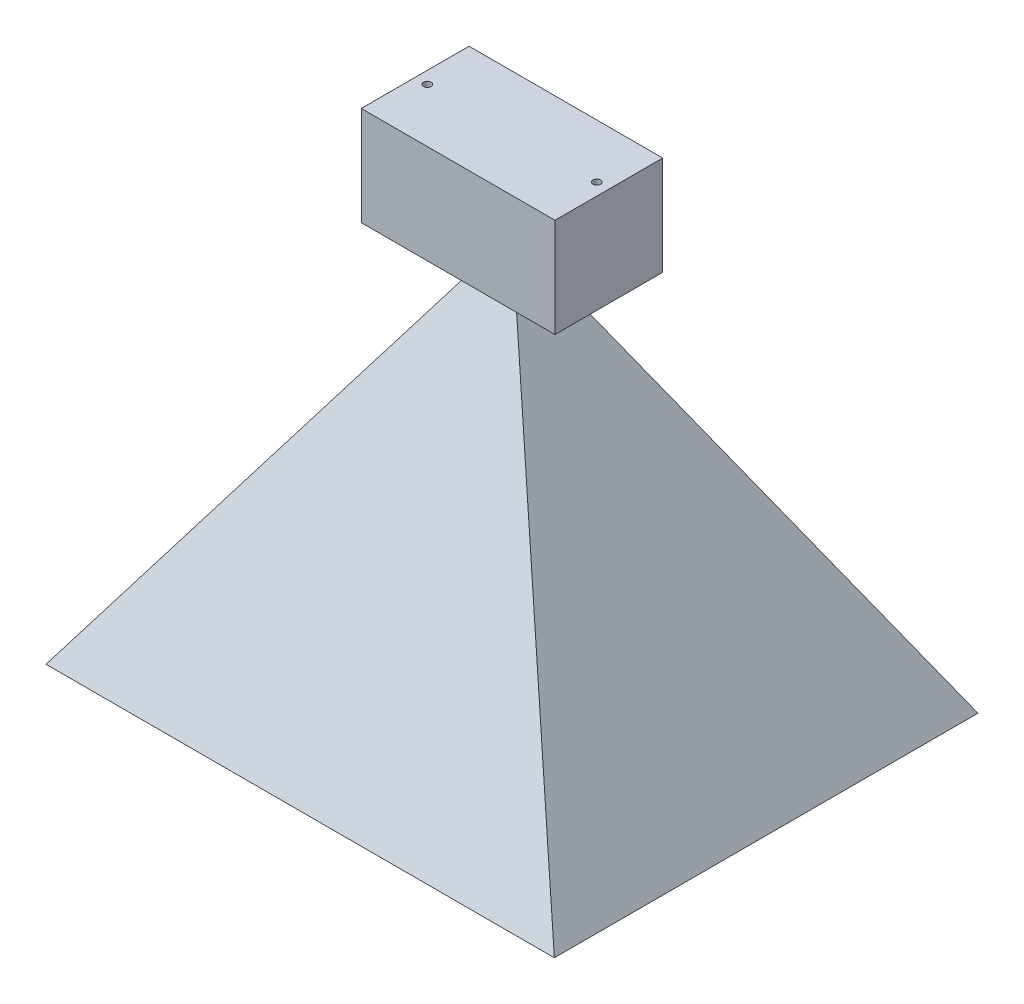
SolidWorks part; units mm, degrees
ref_plane "Front Plane" through (0, 0, 0) normal (0, 0, 1) x (1, 0, 0)
ref_plane "Top Plane" through (0, 0, 0) normal (0, 1, 0) x (1, 0, 0)
ref_plane "Right Plane" through (0, 0, 0) normal (1, 0, 0) x (0, 0, -1)
ref_plane "distance of measurement" through (0, 114.3, 0) normal (0, 1, 0) x (1, 0, 0)
sketch "Sketch1" plane through (0, 0, 0) normal (0, 1, 0) x (1, 0, 0)
  line L1 (-76.2, -63.5) -> (76.2, -63.5)
  line L2 (-76.2, -63.5) -> (-76.2, 63.5)
  line L3 (-76.2, 63.5) -> (76.2, 63.5)
  line L4 (76.2, -63.5) -> (76.2, 63.5)
  line L5 (-76.2, -63.5) -> (76.2, 63.5) construction
  line L6 (-76.2, 63.5) -> (76.2, -63.5) construction
  point P0 (0, 0)
  dimension "D1" = 152.4
  dimension "D2" = 127
sketch "Sketch2" plane through (0, 114.3, 0) normal (0, 1, 0) x (1, 0, 0)
  line L0 (-76.2, -63.5) -> (76.2, 63.5) construction
  line L1 (-2.4698, -2.0581) -> (2.4698, -2.0581)
  line L2 (-2.4698, -2.0581) -> (-2.4698, 2.0581)
  line L3 (-2.4698, 2.0581) -> (2.4698, 2.0581)
  line L4 (2.4698, -2.0581) -> (2.4698, 2.0581)
  line L5 (-2.4698, -2.0581) -> (2.4698, 2.0581) construction
  line L6 (-2.4698, 2.0581) -> (2.4698, -2.0581) construction
  point P0 (0, 0)
loft "FOV" add profiles "Sketch2", "Sketch1" connector at (-2.4698, 114.3, 2.0581) connector at (-76.2, 0, 63.5)
sketch "Sketch3" plane through (0, 114.3, 0) normal (0, 1, 0) x (1, 0, 0)
  circle A0 centre (0, 0) radius 8.509
  dimension "D1" = 17.018
extrude "camera lens" add sketch "Sketch3" along normal blind 0.254
sketch "Sketch4" plane through (0, 114.554, 0) normal (0, 1, 0) x (1, 0, 0)
  line L1 (29.0322, -16.1544) -> (-29.0322, -16.1544)
  line L2 (29.0322, -16.1544) -> (29.0322, 16.1544)
  line L3 (29.0322, 16.1544) -> (-29.0322, 16.1544)
  line L4 (-29.0322, -16.1544) -> (-29.0322, 16.1544)
  line L5 (29.0322, -16.1544) -> (-29.0322, 16.1544) construction
  line L6 (29.0322, 16.1544) -> (-29.0322, -16.1544) construction
  point P0 (0, 0)
  dimension "D1" = 58.0644
  dimension "D2" = 32.3088
extrude "camera holder" add sketch "Sketch4" along normal blind 29.6672
ref_point "centre of vision"
ref_point "direction reference"
sketch "reference points sketch" plane through (0, 0, 0) normal (0, -1, 0) x (1, 0, 0)
  line L0 (-76.2, 63.5) -> (76.2, 63.5) construction
  line L1 (76.2, 63.5) -> (76.2, -63.5) construction
  line L2 (76.2, -63.5) -> (-76.2, -63.5) construction
  line L3 (-76.2, -63.5) -> (-76.2, 63.5) construction
  line L4 (-76.2, 63.5) -> (76.2, -63.5) construction
  line L5 (-76.2, -63.5) -> (76.2, 63.5) construction
  point P0 (0, 63.5)
  point P1 (76.2, 0)
  point P4 (0, -63.5)
  point P7 (-76.2, 0)
  point P10 (-38.1, 0)
  point P13 (38.1, 0)
  point P14 (0, 31.75)
  point P15 (0, -31.75)
  point P16 (38.1, -31.75)
  point P17 (38.1, 31.75)
  point P20 (-38.1, 31.75)
  point P23 (-38.1, -31.75)
  point P24 (-76.2, 63.5)
  point P26 (76.2, 63.5)
  point P28 (76.2, -63.5)
  point P30 (-76.2, -63.5)
  dimension "D1" = 31.75
  dimension "D2" = 0
  dimension "D3" = 38.1
  dimension "D4" = 31.75
  dimension "D5" = 31.75
  dimension "D6" = 38.1
  dimension "D7" = 38.1
  dimension "D8" = 31.75
  dimension "D9" = 38.1
  dimension "D10" = 31.75
  dimension "D11" = 38.1
  dimension "D12" = 38.1
ref_point "direction reference 0"
ref_point "direction reference 1"
ref_point "direction reference 2"
ref_point "direction reference 3"
ref_point "direction reference 4"
ref_point "direction reference 5"
ref_point "direction reference 6"
ref_point "direction reference 7"
ref_point "direction reference 8"
ref_point "direction reference 9"
ref_point "direction reference 10"
ref_point "direction reference 11"
ref_point "direction reference 12"
ref_point "direction reference 13"
ref_point "direction reference 14"
ref_point "direction reference 15"
hole_wizard "#4-40 Tapped Hole1" positions "Sketch6" profile "Sketch5" tap size "#4-40" standard "ANSI Inch" end condition up to next
sketch "Sketch6" plane through (0, 144.2212, 0) normal (0, 1, 0) x (1, 0, 0)
  point P0 (-25.4, 0)
  point P2 (25.4, 0)
  dimension "D1" = 25.4
  dimension "D2" = 25.4
sketch "Sketch5" plane through (-25.4, 144.2212, 0) normal (1, 0, 0) x (0, 0, 1)
  line L0 (0, 0) -> (0, 29.6672)
  line L1 (0, 29.6672) -> (1.1303, 29.6672)
  line L2 (1.1303, 29.6672) -> (1.1303, 0)
  line L5 (1.1303, 0) -> (0, 0)
  line L11 (0, -6.35) -> (0, 107.95) construction
  dimension "Thru Tap Drill Dia." = 2.2606
  dimension "Thru Tap Drill Depth" = 29.6672
cosmetic thread "Hole Thread1" parameters "D2"=2.8448
cosmetic thread "Hole Thread2" parameters "D2"=2.8448
ref_point "z-basis"
ref_point "y-basis"
